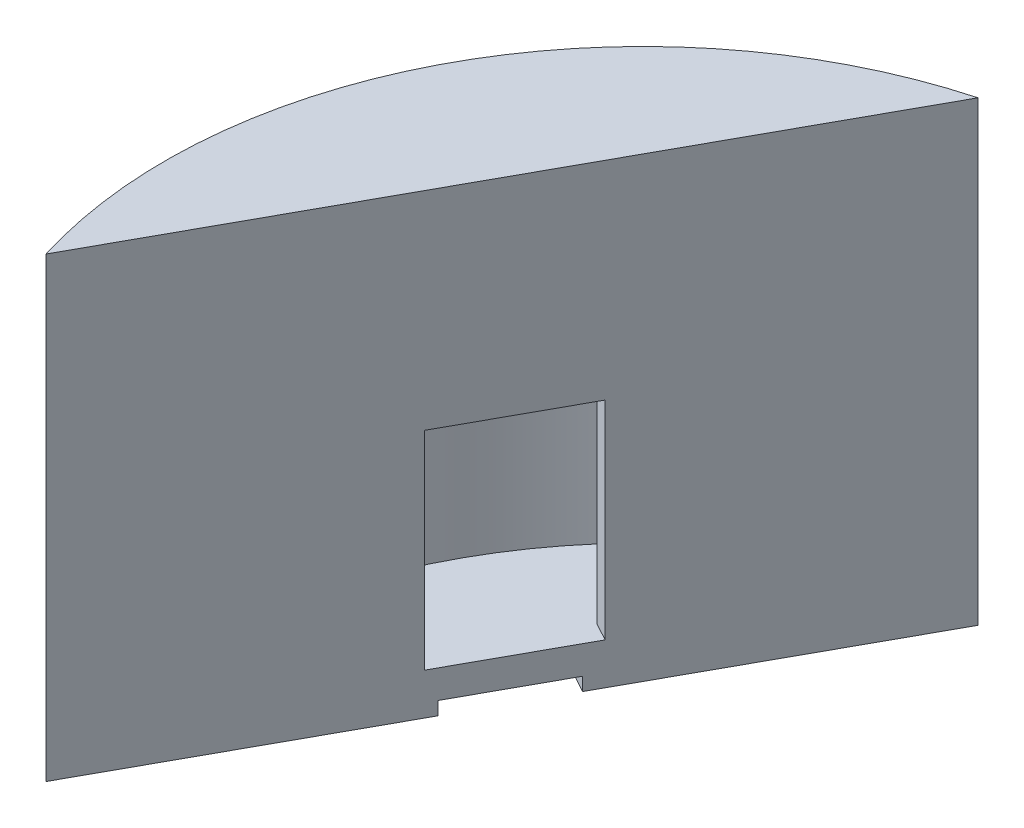
SolidWorks part; units mm, degrees
ref_plane "Front Plane" through (0, 0, 0) normal (0, 0, 1) x (1, 0, 0)
ref_plane "Top Plane" through (0, 0, 0) normal (0, 1, 0) x (1, 0, 0)
ref_plane "Right Plane" through (0, 0, 0) normal (1, 0, 0) x (0, 0, -1)
sketch "Sketch1" plane through (0, 0, 0) normal (0, 1, 0) x (1, 0, 0)
  circle A0 centre (0, 0) radius 69.85
  circle A1 centre (0, 0) radius 73.025
  dimension "D1" = 139.7
  dimension "D2" = 146.05
extrude "Boss-Extrude1" add sketch "Sketch1" along normal blind 63.5
sketch "Sketch2" plane through (0, 0, 0) normal (0, -1, 0) x (1, 0, 0)
  circle A0 centre (0, 0) radius 73.025
  dimension "D1" = 146.05
extrude "Boss-Extrude2" add sketch "Sketch2" along normal blind 6.35
sketch "Sketch3" plane through (0, 0, 0) normal (0, 1, 0) x (1, 0, 0)
  line L1 (-67.6153, -17.527) -> (-21.4092, 66.4881)
  circle A1 centre (0, 0) radius 69.85 construction
  arc A2 (-21.4092, 66.4881) -> (-67.6153, -17.527) centre (0, 0) ccw
  dimension "D1" = 50.8
extrude "Boss-Extrude3" add sketch "Sketch3" along normal blind 63.5
sketch "Sketch4" plane through (0, 63.5, 0) normal (0, 1, 0) x (1, 0, 0)
  line L0 (-25.7919, 64.9138) -> (-68.6329, -12.9827)
  line L1 (-67.6153, -17.527) -> (-21.4092, 66.4881) construction
  arc A0 (-25.7919, 64.9138) -> (-68.6329, -12.9827) centre (0, 0) ccw
  dimension "D2" = 69.85
  dimension "D1" = 88.9
extrude "Cut-Extrude2" cut sketch "Sketch4" against normal blind 57.15 from offset 6.35 offset against normal yes
ref_plane "Plane1" through (-42.2867, 0, -23.2565) normal (0.8762, 0, 0.4819) x (0.4819, 0, -0.8762)
sketch "Sketch6" plane through (-42.2867, 0, -23.2565) normal (0.8762, 0, 0.4819) x (0.4819, 0, -0.8762)
  line L0 (-47.9414, 0) -> (47.9414, 0) construction
  line L5 (-9.8414, 31.75) -> (10.4786, 31.75)
  line L6 (-9.8414, 31.75) -> (-9.8414, 0)
  line L7 (-9.8414, 0) -> (10.4786, 0)
  line L8 (10.4786, 31.75) -> (10.4786, 0)
  line L19 (-47.9414, 63.5) -> (-47.9414, 0) construction
  dimension "D1" = 38.1
  dimension "D2" = 31.75
  dimension "D6" = 20.32
extrude "Cut-Extrude4" cut sketch "Sketch6" against normal blind 31.75 from offset 19.05
sketch "Sketch7" plane through (0, 63.5, 0) normal (0, 1, 0) x (1, 0, 0)
  line L0 (-72.6096, -26.608) -> (-10.1714, 86.9215)
  line L1 (-10.1714, 86.9215) -> (114.9599, 65.8058)
  line L2 (114.9599, 65.8058) -> (122.5488, -33.7487)
  line L3 (122.5488, -33.7487) -> (41.0179, -93.9807)
  line L4 (41.0179, -93.9807) -> (-75.6034, -72.6768)
  line L5 (-75.6034, -72.6768) -> (-72.6096, -26.608)
  line L6 (-67.6153, -17.527) -> (-21.4092, 66.4881) construction
extrude "Cut-Extrude5" cut sketch "Sketch7" against normal blind 1016
sketch "Sketch8" plane through (-44.5123, 0, -24.4806) normal (0.8762, 0, 0.4819) x (0.4819, 0, -0.8762)
  line L0 (-52.4596, -6.35) -> (52.4596, -6.35) construction
  line L1 (-8.3174, -6.35) -> (7.9386, -6.35)
  line L2 (-8.3174, -6.35) -> (-8.3174, -4.318)
  line L3 (-8.3174, -4.318) -> (7.9386, -4.318)
  line L4 (7.9386, -6.35) -> (7.9386, -4.318)
  line L5 (-9.8414, 0) -> (-9.8414, 31.75) construction
  line L6 (10.4786, 31.75) -> (10.4786, 0) construction
  dimension "D1" = 1.524
  dimension "D2" = 2.54
  dimension "D3" = 2.032
extrude "Cut-Extrude6" cut sketch "Sketch8" against normal blind 7.62
